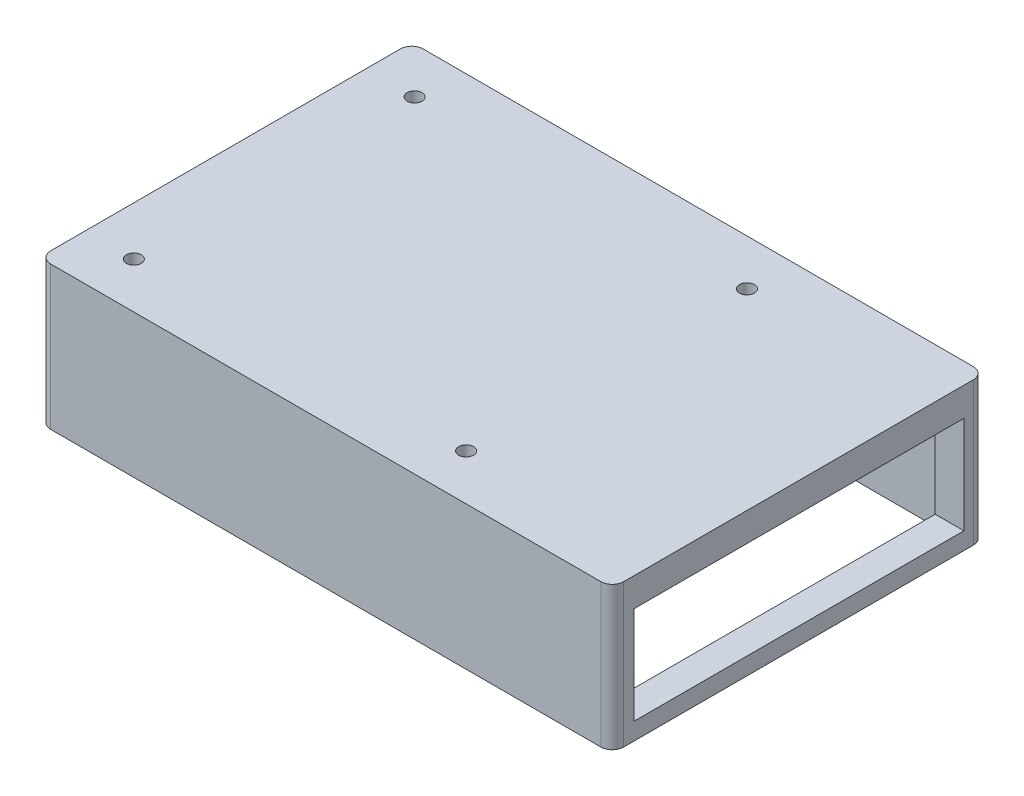
SolidWorks part; units mm, degrees
material "Alumina"
ref_plane "Front Plane" through (0, 0, 0) normal (0, 0, 1) x (1, 0, 0)
ref_plane "Top Plane" through (0, 0, 0) normal (0, 1, 0) x (1, 0, 0)
ref_plane "Right Plane" through (0, 0, 0) normal (1, 0, 0) x (0, 0, -1)
sketch "Sketch1" plane through (0, 0, 0) normal (0, 1, 0) x (1, 0, 0)
  line L1 (-45, -30) -> (45, -30)
  line L2 (-45, -30) -> (-45, 30)
  line L3 (-45, 30) -> (45, 30)
  line L4 (45, -30) -> (45, 30)
  line L5 (-45, -30) -> (45, 30) construction
  line L6 (-45, 30) -> (45, -30) construction
  line L7 (-50, 32.5) -> (50, 32.5)
  line L8 (-50, 32.5) -> (-50, -32.5)
  line L9 (-50, -32.5) -> (50, -32.5)
  line L10 (50, 32.5) -> (50, -32.5)
  line L11 (-50, 32.5) -> (50, -32.5) construction
  line L12 (-50, -32.5) -> (50, 32.5) construction
  point P0 (0, 0)
  point P5 (0, 0)
  dimension "D1" = 90
  dimension "D2" = 60
  dimension "D3" = 100
  dimension "D4" = 65
extrude "Boss-Extrude2" add sketch "Sketch1" along normal blind 25 contours L7 L10 L9 L8
extrude "Cut-Extrude1" cut sketch "Sketch1<5>" along normal blind 22 contours L4 L3 L2 L1
sketch "Sketch1<5>" plane through (0, 0, 0) normal (0, 1, 0) x (1, 0, 0) same geometry as "Sketch1"
sketch "Sketch3" plane through (0, 22, 0) normal (0, -1, 0) x (1, 0, 0)
  line L1 (-45, 30) -> (-45, -30) construction
  circle A0 centre (-41.5, 24.5) radius 1.3
  circle A1 centre (-41.5, -24.5) radius 1.3
  circle A2 centre (16.5, -24.5) radius 1.3
  circle A3 centre (16.5, 24.5) radius 1.3
  dimension "D4" = 3.5
  dimension "D5" = 58
  dimension "D3" = 49
  dimension "D7" = 58
extrude "Cut-Extrude2" cut sketch "Sketch3" against normal blind 18
fillet "Fillet2" radius 2 1 edges at (50, 12.5, 32.5) type face fillet first side face at (0, 12.5, 32.5) second side face at (50, 12.5, 0)
fillet "Fillet3" radius 2 1 edges at (-50, 12.5, 32.5) type face fillet first side face at (-50, 12.5, 0) second side face at (-1, 12.5, 32.5)
fillet "Fillet4" radius 2 1 edges at (-50, 12.5, -32.5) type face fillet first side face at (0, 12.5, -32.5) second side face at (-50, 12.5, -1)
fillet "Fillet5" radius 2 1 edges at (50, 12.5, -32.5) type face fillet first side face at (50, 12.5, -1) second side face at (1, 12.5, -32.5)
sketch "Sketch5" plane through (0, 0, -32.5) normal (0, 0, -1) x (-1, 0, 0)
  line L0 (48, 0) -> (48, 25) construction
  line L1 (2, 22) -> (39, 22)
  line L2 (2, 22) -> (2, 15.2794)
  line L3 (2, 15.2794) -> (39, 15.2794)
  line L4 (39, 22) -> (39, 15.2794)
  line L5 (48, 25) -> (-48, 25) construction
  dimension "D1" = 9
  dimension "D2" = 37
  dimension "D3" = 3
extrude "Cut-Extrude3" cut sketch "Sketch5" against normal blind 10
sketch "Sketch6" plane through (50, 0, 0) normal (1, 0, 0) x (0, 0, -1)
  line L0 (30.5, 0) -> (-30.5, 0) construction
  line L1 (-28.7137, 20) -> (28.861, 20)
  line L2 (-28.7137, 20) -> (-28.7137, 3)
  line L3 (-28.7137, 3) -> (28.861, 3)
  line L4 (28.861, 20) -> (28.861, 3)
  dimension "D1" = 3
  dimension "D2" = 17
extrude "Cut-Extrude4" cut sketch "Sketch6" against normal blind 10
